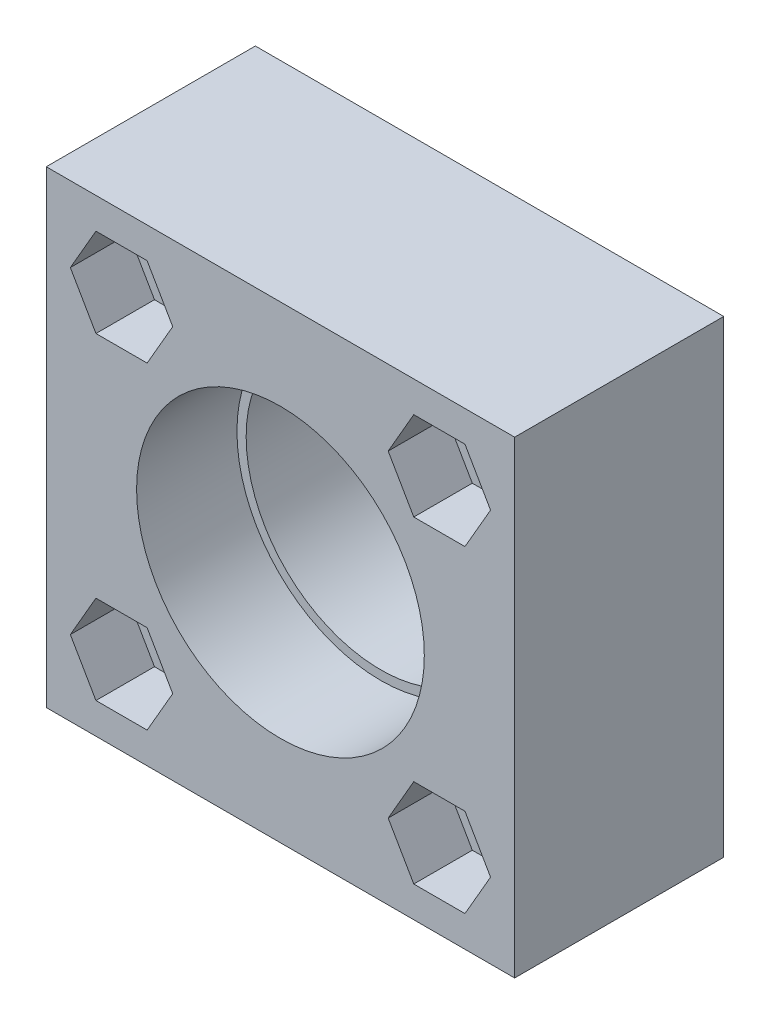
SolidWorks part; units mm, degrees
ref_plane "Alzado" through (0, 0, 0) normal (0, 0, 1) x (1, 0, 0)
ref_plane "Planta" through (0, 0, 0) normal (0, 1, 0) x (1, 0, 0)
ref_plane "Vista lateral" through (0, 0, 0) normal (1, 0, 0) x (0, 0, -1)
sketch "Croquis1" plane through (0, 0, 0) normal (0, 0, 1) x (1, 0, 0)
  line L1 (-14, -14) -> (14, -14)
  line L2 (-14, -14) -> (-14, 14)
  line L3 (-14, 14) -> (14, 14)
  line L4 (14, -14) -> (14, 14)
  line L5 (-14, -14) -> (14, 14) construction
  line L6 (-14, 14) -> (14, -14) construction
  circle A0 centre (0, 0) radius 8.05
  dimension "D1" = 16.1
  dimension "D2" = 28
  dimension "D3" = 28
extrude "Saliente-Extruir1" add sketch "Croquis1" along normal mid plane 6.5
sketch "Croquis2" plane through (0, 0, 3.25) normal (0, 0, 1) x (1, 0, 0)
  line L4 (14, -14) -> (14, 14)
  line L5 (14, 14) -> (-14, 14)
  line L6 (-14, 14) -> (-14, -14)
  line L7 (-14, -14) -> (14, -14)
  line L8 (14, -14) -> (14, 14)
  line L9 (14, 14) -> (-14, 14)
  line L10 (-14, 14) -> (-14, -14)
  line L11 (-14, -14) -> (14, -14)
  circle A0 centre (0, 0) radius 8.6
  dimension "D2" = 17.2
  dimension "D1" = 0
extrude "Saliente-Extruir2" add sketch "Croquis2" along normal blind 6
sketch "Croquis3" plane through (0, 0, 9.25) normal (0, 0, 1) x (1, 0, 0)
  line L0 (-9.5, 9.5) -> (9.5, 9.5) construction
  line L1 (9.5, 9.5) -> (9.5, -9.5) construction
  line L2 (9.5, -9.5) -> (-9.5, -9.5) construction
  line L3 (-9.5, -9.5) -> (-9.5, 9.5) construction
  line L5 (0, 13.0603) -> (0, -13.8489) construction
  line L6 (15.5492, 0) -> (-17.9148, 0) construction
  line L7 (11.03, 12.15) -> (7.97, 12.15)
  line L8 (-6.44, 9.5) -> (-7.97, 12.15)
  line L9 (-7.97, 12.15) -> (-11.03, 12.15)
  line L10 (-11.03, 12.15) -> (-12.56, 9.5)
  line L11 (-12.56, 9.5) -> (-11.03, 6.85)
  line L12 (-11.03, 6.85) -> (-7.97, 6.85)
  line L13 (-7.97, 6.85) -> (-6.44, 9.5)
  line L14 (7.97, 12.15) -> (6.44, 9.5)
  line L15 (6.44, 9.5) -> (7.97, 6.85)
  line L16 (7.97, 6.85) -> (11.03, 6.85)
  line L17 (11.03, 6.85) -> (12.56, 9.5)
  line L18 (12.56, 9.5) -> (11.03, 12.15)
  line L19 (-7.97, -6.85) -> (-11.03, -6.85)
  line L20 (-11.03, -6.85) -> (-12.56, -9.5)
  line L21 (-12.56, -9.5) -> (-11.03, -12.15)
  line L22 (-11.03, -12.15) -> (-7.97, -12.15)
  line L23 (-7.97, -12.15) -> (-6.44, -9.5)
  line L24 (-6.44, -9.5) -> (-7.97, -6.85)
  line L25 (11.03, -6.85) -> (7.97, -6.85)
  line L26 (7.97, -6.85) -> (6.44, -9.5)
  line L27 (6.44, -9.5) -> (7.97, -12.15)
  line L28 (7.97, -12.15) -> (11.03, -12.15)
  line L29 (11.03, -12.15) -> (12.56, -9.5)
  line L30 (12.56, -9.5) -> (11.03, -6.85)
  circle A0 centre (-9.5, 9.5) radius 1.5 construction
  circle A1 centre (-9.5, -9.5) radius 1.5 construction
  circle A2 centre (9.5, -9.5) radius 1.5 construction
  circle A3 centre (9.5, 9.5) radius 1.5 construction
  circle A4 centre (-9.5, 9.5) radius 2.65 construction
  circle A5 centre (9.5, 9.5) radius 2.65 construction
  circle A6 centre (-9.5, -9.5) radius 2.65 construction
  circle A7 centre (9.5, -9.5) radius 2.65 construction
  point P13 (0, -9.5)
  point P14 (-9.5, 0)
  dimension "D1" = 3
  dimension "D2" = 19
  dimension "D3" = 19
  dimension "D4" = 5.3
extrude "Cortar-Extruir1" cut sketch "Croquis3" against normal blind 3.5
sketch "Croquis6" plane through (0, 0, -3.25) normal (0, 0, -1) x (-1, 0, 0)
  line L0 (-9.5, 9.5) -> (9.5, 9.5) construction
  line L1 (9.5, 9.5) -> (9.5, -9.5) construction
  line L2 (9.5, -9.5) -> (-9.5, -9.5) construction
  line L3 (-9.5, -9.5) -> (-9.5, 9.5) construction
  line L4 (0, 17.9373) -> (0, -16.6332) construction
  line L5 (16.9599, 0) -> (-18.6245, 0) construction
  circle A0 centre (-9.5, 9.5) radius 1.5
  circle A1 centre (9.5, 9.5) radius 1.5
  circle A2 centre (9.5, -9.5) radius 1.5
  circle A3 centre (-9.5, -9.5) radius 1.5
  point P13 (0, 9.5)
  point P14 (-9.5, 0)
  dimension "D1" = 3
  dimension "D2" = 19
  dimension "D3" = 19
extrude "Cortar-Extruir2" cut sketch "Croquis6" against normal blind 23.5
